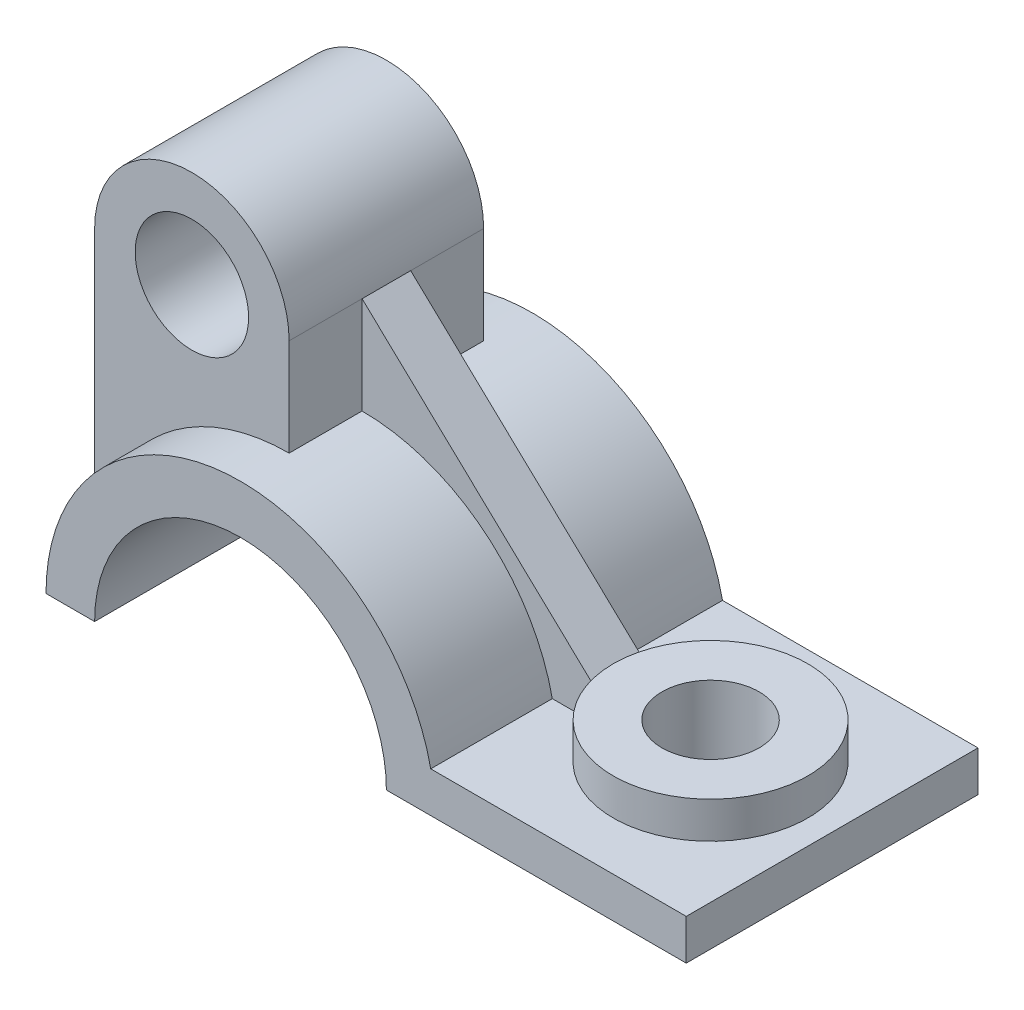
SolidWorks part; units mm, degrees
ref_plane "Front Plane" through (0, 0, 0) normal (0, 0, 1) x (1, 0, 0)
ref_plane "Top Plane" through (0, 0, 0) normal (0, 1, 0) x (1, 0, 0)
ref_plane "Right Plane" through (0, 0, 0) normal (1, 0, 0) x (0, 0, -1)
sketch "Sketch1" plane through (0, 0, 0) normal (0, 0, 1) x (1, 0, 0)
  line L0 (0, 0) -> (0, -23909.6963) construction
  line L1 (0, 0) -> (-23909.6963, 0) construction
  line L2 (-24, 0) -> (55, 0)
  line L3 (55, 0) -> (55, 5)
  line L4 (55, 5) -> (23.4734, 5)
  line L5 (-24, 0) -> (-24, 36)
  line L6 (0, 36) -> (0, 24)
  arc A0 (24, 0) -> (-24, 0) centre (0, 0) ccw
  arc A1 (18, 0) -> (-18, 0) centre (0, 0) ccw
  arc A2 (-24, 36) -> (0, 36) centre (-12, 36) cw
  circle A3 centre (-12, 36) radius 7
  dimension "D1" = 18
  dimension "D2" = 24
  dimension "D5" = 14
  dimension "D3" = 55
  dimension "D4" = 5
  dimension "D6" = 36
extrude "Boss-Extrude1" add sketch "Sketch1" along normal mid plane 36 contours A0 L2 L3 L4 | A1 L2 A0 region at (-16.5911, 16.5911, 0) region at (39.4122, 2.507, 0)
extrude "Boss-Extrude2" add sketch "Sketch1<3>" along normal mid plane 24 contours A2 L5 A0 L6 A3 region at (-23.4633, 18, 0)
sketch "Sketch1<3>" plane through (0, 0, 0) normal (0, 0, 1) x (1, 0, 0) same geometry as "Sketch1"
sketch "Sketch2" plane through (0, 5, 0) normal (0, 1, 0) x (1, 0, 0)
  circle A0 centre (40, 0) radius 12
  point P2 (0, 0)
  dimension "D1" = 40
  dimension "D2" = 24
extrude "Boss-Extrude3" add sketch "Sketch2" along normal mid plane 9
sketch "Sketch3" plane through (0, 0, 0) normal (0, 0, 1) x (1, 0, 0)
  line L0 (0, 36) -> (28, 9.5)
  line L1 (0, 36) -> (0, 24) construction
  arc A0 (0, 36) -> (-24, 36) centre (-12, 36) ccw construction
rib "Rib1" sketch "Sketch3" sketch "Sketch3" thickness 6 extrusion direction parallel to sketch draft on no parameters "D1"=6
hole_wizard "Ø12.0mm Dowel Hole1" positions "Sketch4" profile "Sketch5" hole size "Ø12.0" standard "AS" end condition through all
sketch "Sketch4" plane through (0, 9.5, 0) normal (0, 1, 0) x (1, 0, 0)
  point P0 (40, 0)
sketch "Sketch5" plane through (40, 9.5, 0) normal (1, 0, 0) x (0, 0, 1)
  line L0 (0, 0) -> (0, 9.5)
  line L1 (0, 9.5) -> (6, 9.5)
  line L2 (6, 9.5) -> (6, 0)
  line L5 (6, 0) -> (0, 0)
  line L11 (0, -6.35) -> (0, 107.95) construction
  dimension "Thru Hole Dia." = 12
  dimension "Thru Hole Depth" = 9.5
